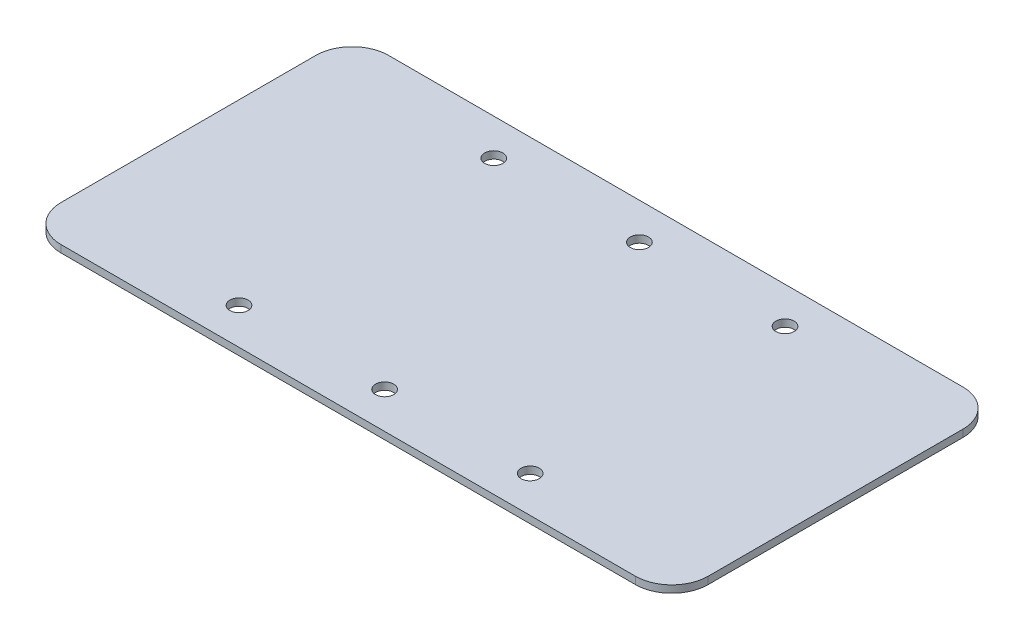
SolidWorks part; units mm, degrees
ref_plane "Front Plane" through (0, 0, 0) normal (0, 0, 1) x (1, 0, 0)
ref_plane "Top Plane" through (0, 0, 0) normal (0, 1, 0) x (1, 0, 0)
ref_plane "Right Plane" through (0, 0, 0) normal (1, 0, 0) x (0, 0, -1)
sketch "Sketch1" plane through (0, 0, 0) normal (0, 1, 0) x (1, 0, 0)
  line L0 (0, -35) -> (0, 35)
  line L1 (-88.9, -45) -> (88.9, -45)
  line L2 (-88.9, -45) -> (-88.9, 45)
  line L3 (-88.9, 45) -> (88.9, 45)
  line L4 (88.9, -45) -> (88.9, 45)
  line L5 (-88.9, -45) -> (88.9, 45) construction
  line L6 (-88.9, 45) -> (88.9, -45) construction
  line L7 (-88.9, 0) -> (88.9, 0) construction
  line L8 (40, -35) -> (40, 35)
  line L9 (-40, -35) -> (-40, 35)
  circle A0 centre (0, 35) radius 2.5
  circle A1 centre (0, -35) radius 2.5
  circle A2 centre (40, 35) radius 2.5
  circle A3 centre (40, -35) radius 2.5
  circle A4 centre (-40, 35) radius 2.5
  circle A5 centre (-40, -35) radius 2.5
  point P0 (0, 0)
  point P9 (0, 0)
  dimension "D4" = 5
  dimension "D1" = 177.8
  dimension "D2" = 90
  dimension "D3" = 70
  dimension "D7" = 40
  dimension "D8" = 40
  dimension "D5" = 2
  dimension "D6" = 2
extrude "Boss-Extrude1" add sketch "Sketch1" along normal blind 2 contours L1 L4 L3 L2 A1 A0 region at (-86.9072, 0, 0)
fillet "Fillet1" radius 10 4 edges at (88.9, 1, 45) (88.9, 1, -45) (-88.9, 1, -45) (-88.9, 1, 45)
equation "\"D\"=70"
equation "\"D3@Sketch1\"=\"D\""
